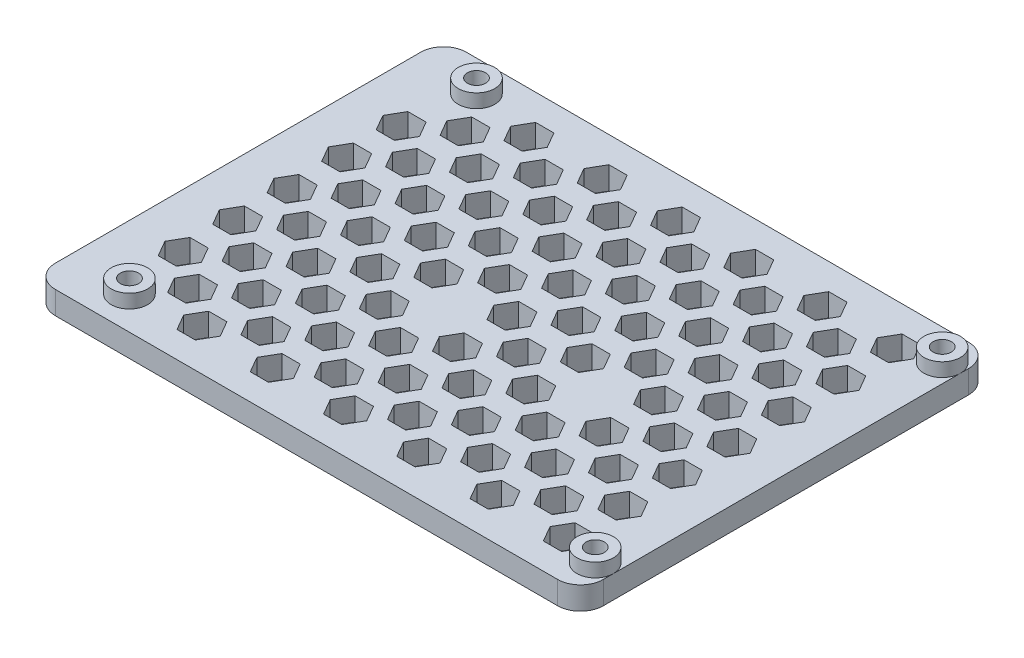
SolidWorks part; units mm, degrees
ref_plane "Front Plane" through (0, 0, 0) normal (0, 0, 1) x (1, 0, 0)
ref_plane "Top Plane" through (0, 0, 0) normal (0, 1, 0) x (1, 0, 0)
ref_plane "Right Plane" through (0, 0, 0) normal (1, 0, 0) x (0, 0, -1)
sketch "Sketch2" plane through (0, 0, 0) normal (0, 1, 0) x (1, 0, 0)
  line L1 (-60, -45) -> (60, -45)
  line L2 (-60, -45) -> (-60, 45)
  line L3 (-60, 45) -> (60, 45)
  line L4 (60, -45) -> (60, 45)
  line L5 (-60, -45) -> (60, 45) construction
  line L6 (-60, 45) -> (60, -45) construction
  point P0 (0, 0)
  dimension "D1" = 120
  dimension "D2" = 90
extrude "Boss-Extrude1" add sketch "Sketch2" along normal blind 5
sketch "Sketch3" plane through (0, 0, 0) normal (0, -1, 0) x (1, 0, 0)
  line L0 (-60, 45) -> (60, 45) construction
  line L1 (-60, -45) -> (-60, 45) construction
  circle A0 centre (-55, 40) radius 2.25
  circle A1 centre (7, 40) radius 2.25
  circle A2 centre (24, 6) radius 2.25
  circle A3 centre (-7, 4) radius 2.25
  point P12 (-6.8651, 3.1112)
  dimension "D3" = 4.5
  dimension "D1" = 5
  dimension "D2" = 5
  dimension "D4" = 62
  dimension "D5" = 34
  dimension "D6" = 17
  dimension "D7" = 31
  dimension "D8" = 2
extrude "Cut-Extrude1" cut sketch "Sketch3" against normal blind 3
sketch "Sketch4" plane through (0, 5, 0) normal (0, 1, 0) x (1, 0, 0)
  line L0 (60, -45) -> (60, 45) construction
  circle A0 centre (-46, 38.2204) radius 4
  circle A1 centre (56, 38.2204) radius 4
  circle A2 centre (56, -37.7796) radius 4
  circle A3 centre (-46, -37.7796) radius 4
  point P8 (-22.3223, 32.5922)
  point P9 (-47.3051, 38.2204)
  dimension "D3" = 8
  dimension "D1" = 76
  dimension "D2" = 102
extrude "Boss-Extrude2" add sketch "Sketch4" along normal blind 3
sketch "Sketch5" plane through (0, 8, 0) normal (0, 1, 0) x (1, 0, 0)
  circle A0 centre (-46, 38.2204) radius 2
  circle A1 centre (56, 38.2204) radius 2
  circle A2 centre (56, -37.7796) radius 2
  circle A3 centre (-46, -37.7796) radius 2
  dimension "D1" = 4
extrude "Cut-Extrude2" cut sketch "Sketch5" against normal blind 6
fillet "Fillet1" radius 5 4 edges at (60, 2.5, -45) (60, 2.5, 45) (-60, 2.5, -45) (-60, 2.5, 45)
sketch "Sketch6" plane through (0, 0, 0) normal (0, -1, 0) x (1, 0, 0)
  line L1 (2, 3.4641) -> (-2, 3.4641)
  line L2 (-2, 3.4641) -> (-4, 0)
  line L3 (-4, 0) -> (-2, -3.4641)
  line L4 (-2, -3.4641) -> (2, -3.4641)
  line L5 (2, -3.4641) -> (4, 0)
  line L6 (4, 0) -> (2, 3.4641)
  circle A0 centre (0, 0) radius 3.4641 construction
  point P1 (53.3022, -39.1777)
  point P9 (0, 0)
  dimension "D1" = 4
sketch "Sketch7" plane through (0, 0, 0) normal (0, -1, 0) x (1, 0, 0)
  line L0 (58.5355, 43.5355) -> (-58.5355, -43.5355)
  line L1 (-58.5355, 43.5355) -> (58.5355, -43.5355)
  arc A0 (-55, 45) -> (-60, 40) centre (-55, 40) ccw construction
  arc A1 (60, 40) -> (55, 45) centre (55, 40) ccw construction
  arc A2 (-60, -40) -> (-55, -45) centre (-55, -40) ccw construction
  arc A3 (55, -45) -> (60, -40) centre (55, -40) ccw construction
extrude "Cut-Extrude4" cut sketch "Sketch6" against normal up to surface (5 mm away) up to face at (-46, 5, 33.7796)
pattern_linear "LPattern2" count 7 spacing 10 along (0.8024, 0, 0.5968) count 7 spacing 10 along (-0.8024, 0, 0.5968) skipping (0, 1), (0, 6), (1, 6), (2, 5), (2, 6), (3, 4), (3, 5), (3, 6), (4, 3), (4, 4), (4, 5), (4, 6), (5, 2), (5, 3), (5, 4), (5, 5), (5, 6), (6, 1), (6, 2), (6, 3), (6, 4), (6, 5), (6, 6) of "Cut-Extrude4"
pattern_linear "LPattern3" count 7 spacing 10 along (-0.8024, 0, -0.5968) count 7 spacing 10 along (-0.8024, 0, 0.5968) skipping (0, 1), (0, 6), (1, 6), (2, 5), (2, 6), (3, 4), (3, 5), (3, 6), (4, 3), (4, 4), (4, 5), (4, 6), (5, 2), (5, 3), (5, 4), (5, 5), (5, 6), (6, 0), (6, 1), (6, 2), (6, 3), (6, 4), (6, 5), (6, 6) of "Cut-Extrude4"
pattern_linear "LPattern4" count 7 spacing 10 along (0.8024, 0, -0.5968) count 7 spacing 10 along (-0.8024, 0, -0.5968) skipping (0, 6), (1, 6), (2, 5), (2, 6), (3, 4), (3, 5), (3, 6), (4, 3), (4, 4), (4, 5), (4, 6), (5, 2), (5, 3), (5, 4), (5, 5), (5, 6), (6, 1), (6, 2), (6, 3), (6, 4), (6, 5), (6, 6) of "Cut-Extrude4"
pattern_linear "LPattern5" count 7 spacing 10 along (0.8024, 0, -0.5968) count 7 spacing 10 along (0.8024, 0, 0.5968) skipping (1, 2), (1, 6), (2, 5), (2, 6), (3, 4), (3, 5), (3, 6), (4, 3), (4, 4), (4, 5), (4, 6), (5, 2), (5, 3), (5, 4), (5, 5), (5, 6), (6, 1), (6, 2), (6, 3), (6, 4), (6, 5), (6, 6) of "Cut-Extrude4"
